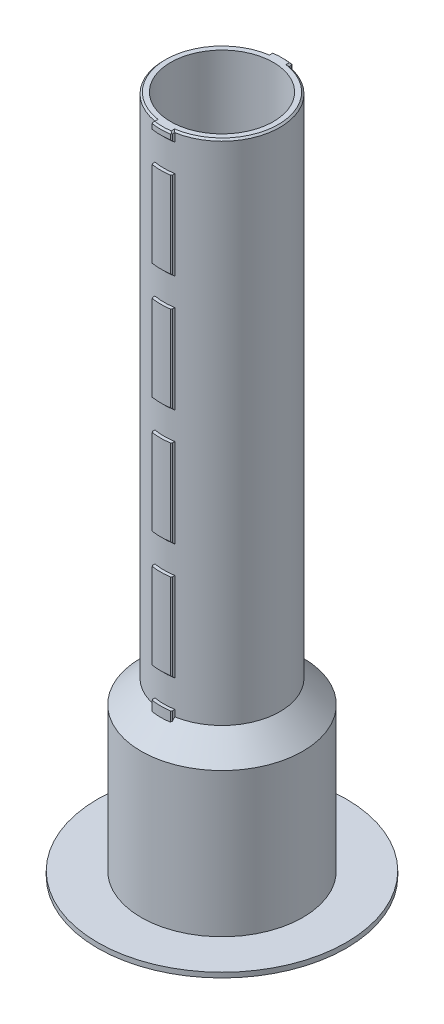
SolidWorks part; units mm, degrees
note: The reader was unsure of these and kept them because the rebuilt part matched: shared geometry of "Sketch4<2>".
ref_plane "Front Plane" through (0, 0, 0) normal (0, 0, 1) x (1, 0, 0)
ref_plane "Top Plane" through (0, 0, 0) normal (0, 1, 0) x (1, 0, 0)
ref_plane "Right Plane" through (0, 0, 0) normal (1, 0, 0) x (0, 0, -1)
sketch "Sketch2" plane through (0, 0, 0) normal (0, 0, 1) x (1, 0, 0)
  line L0 (0, 0) -> (0, 205) construction
  line L1 (22.5, 0) -> (22.5, 44)
  line L5 (24.4, 44.9284) -> (24.4, 0)
  line L6 (24.4, 0) -> (22.5, 0)
  line L7 (22.5, 44) -> (15.5, 51)
  line L9 (17.5, 51.8284) -> (24.4, 44.9284)
  line L10 (17.5, 205) -> (17.5, 51.8284)
  line L11 (15.5, 205) -> (15.5, 51)
  line L12 (17.5, 205) -> (15.5, 205)
  point P10 (0, 0)
  dimension "D1" = 22.5
  dimension "D3" = 44
  dimension "D4" = 1.9
  dimension "D5" = 2
  dimension "D6" = 135
  dimension "D7" = 17.5
  dimension "D8" = 2
  dimension "D9" = 205
revolve "Revolve1" add sketch "Sketch2" angle 360 about L0
sketch "Sketch3" plane through (0, 0, 0) normal (0, -1, 0) x (1, 0, 0)
  circle A0 centre (0, 0) radius 37.5
  circle A3 centre (0, 0) radius 22.5 construction
  circle A4 centre (0, 0) radius 22.5
  dimension "D1" = 75
extrude "Boss-Extrude1" add sketch "Sketch3" against normal blind 1.5
sketch "Sketch4" plane through (0, 205, 0) normal (0, 1, 0) x (1, 0, 0)
  line L0 (0, 18.5) -> (0, -18.5) construction
  line L1 (-3, 18.2551) -> (-3, 17.2409)
  line L2 (3, 18.2551) -> (3, 17.2409)
  line L3 (-3, 18.5) -> (-3, -18.5) construction
  line L4 (3, 18.5) -> (3, -18.5) construction
  line L5 (3, -17.2409) -> (3, -18.2551)
  line L6 (-3, -17.2409) -> (-3, -18.2551)
  arc A0 (-3, -18.2551) -> (3, -18.2551) centre (0, 0) ccw
  circle A1 centre (0, 0) radius 17.5 construction
  arc A2 (-3, -17.2409) -> (3, -17.2409) centre (0, 0) ccw
  arc A4 (3, 18.2551) -> (-3, 18.2551) centre (0, 0) ccw
  arc A5 (3, 17.2409) -> (-3, 17.2409) centre (0, 0) ccw
  dimension "D1" = 1
  dimension "D2" = 3
  dimension "D3" = 3
extrude "Boss-Extrude2" add sketch "Sketch4" against normal up to surface (153.1716 mm away) up to face at (0, 51.8284, -17.5)
chamfer "Chamfer4" distance 0.25 angle 45 4 edges at (-3, 127.9142, 18.2551) (3, 127.9142, 18.2551) (3, 127.9142, -18.2551) (-3, 127.9142, -18.2551)
extrude "Cut-Extrude1" cut sketch "Sketch4<2>" against normal blind 8.2 from offset 3 offset against normal yes
sketch "Sketch4<2>" plane through (0, 205, 0) normal (0, 1, 0) x (1, 0, 0) same geometry as "Sketch4"
pattern_linear "LPattern1" count 5 spacing 35 along (0, -1, 0) of "Cut-Extrude1"
chamfer "Chamfer1" distance 1 angle 45 1 edges at (0, 0, -22.5)
chamfer "Chamfer2" distance 0.5 angle 45 12 edges at (3, 205, -17.5964) (-17.5, 205, 0) (-3, 205, 17.5964) (0.0257, 205, -18.5) (-3, 205, -17.623) (-0.0257, 205, 18.5) (3, 205, 17.623) (-2.8519, 205, -18.1532) (2.8773, 205, -18.1229) (2.8519, 205, 18.1532) (-2.8773, 205, 18.1229) (17.5, 205, 0)
chamfer "Chamfer3" distance 1 angle 45 10 edges at (0.0257, 97, -18.5) (0.0257, 132, -18.5) (0.0257, 167, -18.5) (0.0257, 202, -18.5) (0.0257, 62, -18.5) (-0.0257, 62, 18.5) (-0.0257, 97, 18.5) (-0.0257, 132, 18.5) (-0.0257, 167, 18.5) (-0.0257, 202, 18.5)
